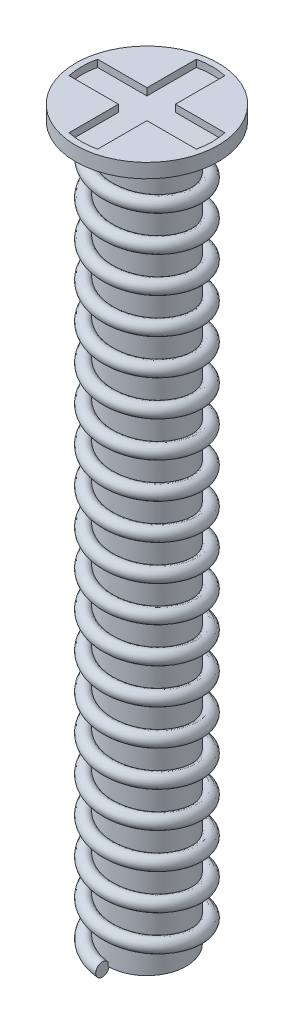
SolidWorks part; units mm, degrees
ref_plane "Alzado" through (0, 0, 0) normal (0, 0, 1) x (1, 0, 0)
ref_plane "Planta" through (0, 0, 0) normal (0, 1, 0) x (1, 0, 0)
ref_plane "Vista lateral" through (0, 0, 0) normal (1, 0, 0) x (0, 0, -1)
sketch "Croquis1" plane through (0, 0, 0) normal (0, 1, 0) x (1, 0, 0)
  circle A0 centre (0, 0) radius 0.55
  dimension "D1" = 1.1
extrude "Saliente-Extruir1" add sketch "Croquis1" along normal blind 10
sketch "Croquis2" plane through (0, 10, 0) normal (0, 1, 0) x (1, 0, 0)
  circle A0 centre (0, 0) radius 1
  dimension "D1" = 2
extrude "Saliente-Extruir2" add sketch "Croquis2" along normal blind 0.2
sketch "Croquis4" plane through (0, 10, 0) normal (0, -1, 0) x (1, 0, 0)
  circle A0 centre (0, 0) radius 0.625
  dimension "D1" = 1.25
curve "Hélice/Espiral1" pitch 0.5 height 10 turns 20
sketch "Croquis5" plane through (0, 0, 0) normal (1, 0, 0) x (0, 0, -1)
  circle A0 centre (-0.625, 0) radius 0.0938
  spline S0 degree 3 poles (-0.625, 10) (-0.625, 9.9896) (-0.5925, 9.9687) (-0.4534, 9.9375) (-0.1761, 9.8958) (0.1761, 9.8542) (0.4534, 9.8125) (0.5925, 9.7812) (0.6413, 9.75) (0.5925, 9.7187) (0.4534, 9.6875) (0.1761, 9.6458) (-0.1761, 9.6042) (-0.4534, 9.5625) (-0.5925, 9.5312) (-0.6413, 9.5) (-0.5925, 9.4687) (-0.4534, 9.4375) (-0.1761, 9.3958) (0.1761, 9.3542) (0.4534, 9.3125) (0.5925, 9.2812) (0.6413, 9.25) (0.5925, 9.2188) (0.4534, 9.1875) (0.1761, 9.1458) (-0.1761, 9.1042) (-0.4534, 9.0625) (-0.5925, 9.0312) (-0.6413, 9) (-0.5925, 8.9687) (-0.4534, 8.9375) (-0.1761, 8.8958) (0.1761, 8.8542) (0.4534, 8.8125) (0.5925, 8.7812) (0.6413, 8.75) (0.5925, 8.7188) (0.4534, 8.6875) (0.1761, 8.6458) (-0.1761, 8.6042) (-0.4534, 8.5625) (-0.5925, 8.5312) (-0.6413, 8.5) (-0.5925, 8.4687) (-0.4534, 8.4375) (-0.1761, 8.3958) (0.1761, 8.3542) (0.4534, 8.3125) (0.5925, 8.2812) (0.6413, 8.25) (0.5925, 8.2187) (0.4534, 8.1875) (0.1761, 8.1458) (-0.1761, 8.1042) (-0.4534, 8.0625) (-0.5925, 8.0312) (-0.6413, 8) (-0.5925, 7.9687) (-0.4534, 7.9375) (-0.1761, 7.8958) (0.1761, 7.8542) (0.4534, 7.8125) (0.5925, 7.7812) (0.6413, 7.75) (0.5925, 7.7187) (0.4534, 7.6875) (0.1761, 7.6458) (-0.1761, 7.6042) (-0.4534, 7.5625) (-0.5925, 7.5312) (-0.6413, 7.5) (-0.5925, 7.4687) (-0.4534, 7.4375) (-0.1761, 7.3958) (0.1761, 7.3542) (0.4534, 7.3125) (0.5925, 7.2812) (0.6413, 7.25) (0.5925, 7.2187) (0.4534, 7.1875) (0.1761, 7.1458) (-0.1761, 7.1042) (-0.4534, 7.0625) (-0.5925, 7.0312) (-0.6413, 7) (-0.5925, 6.9687) (-0.4534, 6.9375) (-0.1761, 6.8958) (0.1761, 6.8542) (0.4534, 6.8125) (0.5925, 6.7812) (0.6413, 6.75) (0.5925, 6.7187) (0.4534, 6.6875) (0.1761, 6.6458) (-0.1761, 6.6042) (-0.4534, 6.5625) (-0.5925, 6.5312) (-0.6413, 6.5) (-0.5925, 6.4687) (-0.4534, 6.4375) (-0.1761, 6.3958) (0.1761, 6.3542) (0.4534, 6.3125) (0.5925, 6.2812) (0.6413, 6.25) (0.5925, 6.2187) (0.4534, 6.1875) (0.1761, 6.1458) (-0.1761, 6.1042) (-0.4534, 6.0625) (-0.5925, 6.0312) (-0.6413, 6) (-0.5925, 5.9687) (-0.4534, 5.9375) (-0.1761, 5.8958) (0.1761, 5.8542) (0.4534, 5.8125) (0.5925, 5.7812) (0.6413, 5.75) (0.5925, 5.7187) (0.4534, 5.6875) (0.1761, 5.6458) (-0.1761, 5.6042) (-0.4534, 5.5625) (-0.5925, 5.5312) (-0.6413, 5.5) (-0.5925, 5.4687) (-0.4534, 5.4375) (-0.1761, 5.3958) (0.1761, 5.3542) (0.4534, 5.3125) (0.5925, 5.2812) (0.6413, 5.25) (0.5925, 5.2187) (0.4534, 5.1875) (0.1761, 5.1458) (-0.1761, 5.1042) (-0.4534, 5.0625) (-0.5925, 5.0312) (-0.6413, 5) (-0.5925, 4.9687) (-0.4534, 4.9375) (-0.1761, 4.8958) (0.1761, 4.8542) (0.4534, 4.8125) (0.5925, 4.7812) (0.6413, 4.75) (0.5925, 4.7187) (0.4534, 4.6875) (0.1761, 4.6458) (-0.1761, 4.6042) (-0.4534, 4.5625) (-0.5925, 4.5312) (-0.6413, 4.5) (-0.5925, 4.4687) (-0.4534, 4.4375) (-0.1761, 4.3958) (0.1761, 4.3542) (0.4534, 4.3125) (0.5925, 4.2812) (0.6413, 4.25) (0.5925, 4.2187) (0.4534, 4.1875) (0.1761, 4.1458) (-0.1761, 4.1042) (-0.4534, 4.0625) (-0.5925, 4.0312) (-0.6413, 4) (-0.5925, 3.9687) (-0.4534, 3.9375) (-0.1761, 3.8958) (0.1761, 3.8542) (0.4534, 3.8125) (0.5925, 3.7812) (0.6413, 3.75) (0.5925, 3.7187) (0.4534, 3.6875) (0.1761, 3.6458) (-0.1761, 3.6042) (-0.4534, 3.5625) (-0.5925, 3.5312) (-0.6413, 3.5) (-0.5925, 3.4687) (-0.4534, 3.4375) (-0.1761, 3.3958) (0.1761, 3.3542) (0.4534, 3.3125) (0.5925, 3.2812) (0.6413, 3.25) (0.5925, 3.2187) (0.4534, 3.1875) (0.1761, 3.1458) (-0.1761, 3.1042) (-0.4534, 3.0625) (-0.5925, 3.0312) (-0.6413, 3) (-0.5925, 2.9687) (-0.4534, 2.9375) (-0.1761, 2.8958) (0.1761, 2.8542) (0.4534, 2.8125) (0.5925, 2.7812) (0.6413, 2.75) (0.5925, 2.7187) (0.4534, 2.6875) (0.1761, 2.6458) (-0.1761, 2.6042) (-0.4534, 2.5625) (-0.5925, 2.5312) (-0.6413, 2.5) (-0.5925, 2.4687) (-0.4534, 2.4375) (-0.1761, 2.3958) (0.1761, 2.3542) (0.4534, 2.3125) (0.5925, 2.2812) (0.6413, 2.25) (0.5925, 2.2187) (0.4534, 2.1875) (0.1761, 2.1458) (-0.1761, 2.1042) (-0.4534, 2.0625) (-0.5925, 2.0312) (-0.6413, 2) (-0.5925, 1.9687) (-0.4534, 1.9375) (-0.1761, 1.8958) (0.1761, 1.8542) (0.4534, 1.8125) (0.5925, 1.7812) (0.6413, 1.75) (0.5925, 1.7187) (0.4534, 1.6875) (0.1761, 1.6458) (-0.1761, 1.6042) (-0.4534, 1.5625) (-0.5925, 1.5312) (-0.6413, 1.5) (-0.5925, 1.4687) (-0.4534, 1.4375) (-0.1761, 1.3958) (0.1761, 1.3542) (0.4534, 1.3125) (0.5925, 1.2812) (0.6413, 1.25) (0.5925, 1.2187) (0.4534, 1.1875) (0.1761, 1.1458) (-0.1761, 1.1042) (-0.4534, 1.0625) (-0.5925, 1.0312) (-0.6413, 1) (-0.5925, 0.9687) (-0.4534, 0.9375) (-0.1761, 0.8958) (0.1761, 0.8542) (0.4534, 0.8125) (0.5925, 0.7812) (0.6413, 0.75) (0.5925, 0.7187) (0.4534, 0.6875) (0.1761, 0.6458) (-0.1761, 0.6042) (-0.4534, 0.5625) (-0.5925, 0.5313) (-0.6413, 0.5) (-0.5925, 0.4688) (-0.4534, 0.4375) (-0.1761, 0.3958) (0.1761, 0.3542) (0.4534, 0.3125) (0.5925, 0.2813) (0.6413, 0.25) (0.5925, 0.2188) (0.4534, 0.1875) (0.1761, 0.1458) (-0.1761, 0.1042) (-0.4534, 0.0625) (-0.5925, 0.0313) (-0.625, 0.0104) (-0.625, 0) knots 0 0 0 0 0.003125 0.00625 0.009375 0.015625 0.01875 0.021875 0.025 0.028125 0.03125 0.034375 0.040625 0.04375 0.046875 0.05 0.053125 0.05625 0.059375 0.065625 0.06875 0.071875 0.075 0.078125 0.08125 0.084375 0.090625 0.09375 0.096875 0.1 0.103125 0.10625 0.109375 0.115625 0.11875 0.121875 0.125 0.128125 0.13125 0.134375 0.140625 0.14375 0.146875 0.15 0.153125 0.15625 0.159375 0.165625 0.16875 0.171875 0.175 0.178125 0.18125 0.184375 0.190625 0.19375 0.196875 0.2 0.203125 0.20625 0.209375 0.215625 0.21875 0.221875 0.225 0.228125 0.23125 0.234375 0.240625 0.24375 0.246875 0.25 0.253125 0.25625 0.259375 0.265625 0.26875 0.271875 0.275 0.278125 0.28125 0.284375 0.290625 0.29375 0.296875 0.3 0.303125 0.30625 0.309375 0.315625 0.31875 0.321875 0.325 0.328125 0.33125 0.334375 0.340625 0.34375 0.346875 0.35 0.353125 0.35625 0.359375 0.365625 0.36875 0.371875 0.375 0.378125 0.38125 0.384375 0.390625 0.39375 0.396875 0.4 0.403125 0.40625 0.409375 0.415625 0.41875 0.421875 0.425 0.428125 0.43125 0.434375 0.440625 0.44375 0.446875 0.45 0.453125 0.45625 0.459375 0.465625 0.46875 0.471875 0.475 0.478125 0.48125 0.484375 0.490625 0.49375 0.496875 0.5 0.503125 0.50625 0.509375 0.515625 0.51875 0.521875 0.525 0.528125 0.53125 0.534375 0.540625 0.54375 0.546875 0.55 0.553125 0.55625 0.559375 0.565625 0.56875 0.571875 0.575 0.578125 0.58125 0.584375 0.590625 0.59375 0.596875 0.6 0.603125 0.60625 0.609375 0.615625 0.61875 0.621875 0.625 0.628125 0.63125 0.634375 0.640625 0.64375 0.646875 0.65 0.653125 0.65625 0.659375 0.665625 0.66875 0.671875 0.675 0.678125 0.68125 0.684375 0.690625 0.69375 0.696875 0.7 0.703125 0.70625 0.709375 0.715625 0.71875 0.721875 0.725 0.728125 0.73125 0.734375 0.740625 0.74375 0.746875 0.75 0.753125 0.75625 0.759375 0.765625 0.76875 0.771875 0.775 0.778125 0.78125 0.784375 0.790625 0.79375 0.796875 0.8 0.803125 0.80625 0.809375 0.815625 0.81875 0.821875 0.825 0.828125 0.83125 0.834375 0.840625 0.84375 0.846875 0.85 0.853125 0.85625 0.859375 0.865625 0.86875 0.871875 0.875 0.878125 0.88125 0.884375 0.890625 0.89375 0.896875 0.9 0.903125 0.90625 0.909375 0.915625 0.91875 0.921875 0.925 0.928125 0.93125 0.934375 0.940625 0.94375 0.946875 0.95 0.953125 0.95625 0.959375 0.965625 0.96875 0.971875 0.975 0.978125 0.98125 0.984375 0.990625 0.99375 0.996875 1 1 1 1 construction
sweep "Barrer1" add profiles "Croquis5" path "Hélice/Espiral1"
sketch "Croquis6" plane through (0, 10.2, 0) normal (0, 1, 0) x (1, 0, 0)
  line L0 (0, 1) -> (0, 0) construction
  line L1 (0, 0) -> (1, 0) construction
  line L2 (0.2, 0.8928) -> (0.2, 0.2)
  line L3 (0.2, 0.2) -> (0.8928, 0.2)
  line L4 (-0.2, 0.8928) -> (-0.2, 0.2)
  line L5 (-0.2, 0.2) -> (-0.8928, 0.2)
  line L6 (0.2, -0.2) -> (0.8928, -0.2)
  line L7 (0.2, -0.8928) -> (0.2, -0.2)
  line L8 (-0.2, -0.8928) -> (-0.2, -0.2)
  line L9 (-0.2, -0.2) -> (-0.8928, -0.2)
  circle A0 centre (0, 0) radius 1 construction
  arc A1 (-0.2, -0.8928) -> (0.2, -0.8928) centre (0, 0) ccw
  arc A2 (0.8928, -0.2) -> (0.8928, 0.2) centre (0, 0) ccw
  arc A3 (0.2, 0.8928) -> (-0.2, 0.8928) centre (0, 0) ccw
  arc A4 (-0.8928, 0.2) -> (-0.8928, -0.2) centre (0, 0) ccw
  dimension "D1" = 0.2
  dimension "D2" = 0.2
extrude "Cortar-Extruir1" cut sketch "Croquis6" against normal blind 0.1
